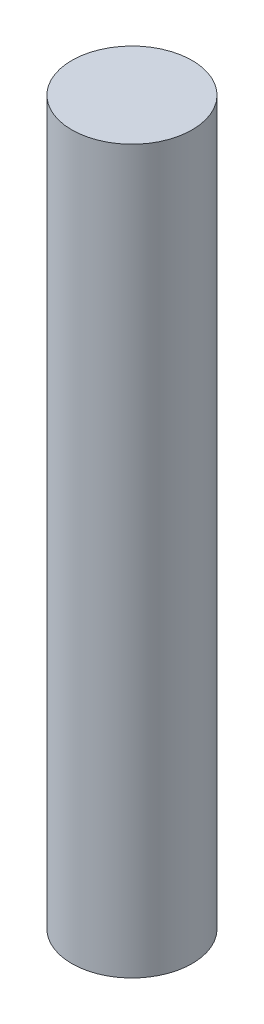
SolidWorks part; units mm, degrees
ref_plane "Front Plane" through (0, 0, 0) normal (0, 0, 1) x (1, 0, 0)
ref_plane "Top Plane" through (0, 0, 0) normal (0, 1, 0) x (1, 0, 0)
ref_plane "Right Plane" through (0, 0, 0) normal (1, 0, 0) x (0, 0, -1)
ref_axis "X" through (-88.99, 0, 0) along (1, 0, 0)
ref_axis "Y" through (0, 55, 0) along (0, -1, 0)
ref_axis "Z" through (0, 0, -88.99) along (0, 0, 1)
sketch "Sketch1" plane through (0, 0, 0) normal (0, 1, 0) x (1, 0, 0)
  circle A0 centre (0, 0) radius 1
  dimension "D1" = 2
extrude "Boss-Extrude1" add sketch "Sketch1" along normal blind 12
